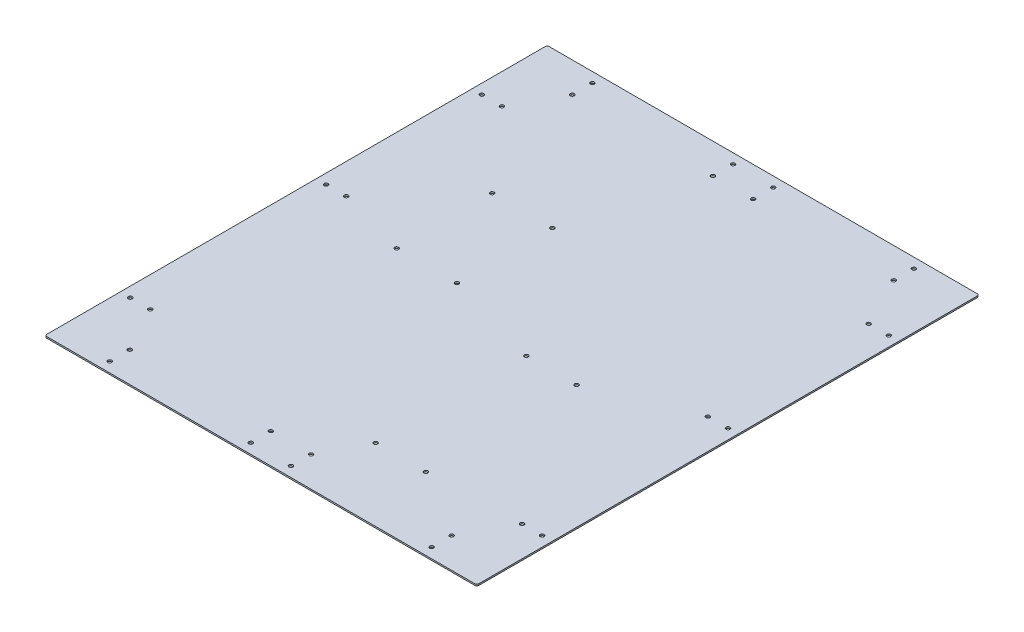
SolidWorks part; units mm, degrees
ref_plane "Front Plane" through (0, 0, 0) normal (0, 0, 1) x (1, 0, 0)
ref_plane "Top Plane" through (0, 0, 0) normal (0, 1, 0) x (1, 0, 0)
ref_plane "Right Plane" through (0, 0, 0) normal (1, 0, 0) x (0, 0, -1)
sketch "Sketch1" plane through (0, 0, 0) normal (0, 1, 0) x (1, 0, 0)
  line L1 (-215, -250) -> (215, -250)
  line L2 (-215, -250) -> (-215, 250)
  line L3 (-215, 250) -> (215, 250)
  line L4 (215, -250) -> (215, 250)
  line L5 (-215, -250) -> (215, 250) construction
  line L6 (-215, 250) -> (215, -250) construction
  point P0 (0, 0)
  dimension "D1" = 430
  dimension "D2" = 500
extrude "Boss-Extrude1" add sketch "Sketch1" along normal blind 1.5
sketch "Sketch6" plane through (0, 1.5, 0) normal (0, 1, 0) x (1, 0, 0)
  circle A0 centre (92.2927, -28) radius 1.95
  circle A1 centre (42.2927, -28) radius 1.95
  circle A2 centre (92.2927, -178) radius 1.95
  circle A3 centre (42.2927, -178) radius 1.95
  dimension "D1" = 50
  dimension "D2" = 150
sketch "Sketch7" plane through (0, 1.5, 0) normal (0, 1, 0) x (1, 0, 0)
  circle A0 centre (-114.98, 95.1924) radius 1.95
  circle A1 centre (-54.98, 95.1924) radius 1.95
  circle A2 centre (-54.98, 0.1924) radius 1.95
  circle A3 centre (-114.98, 0.1924) radius 1.95
  dimension "D1" = 95
  dimension "D2" = 60
sketch "Sketch12" plane through (0, 0, 0) normal (0, -1, 0) x (-1, 0, 0)
  line L0 (215, -250) -> (-215, -250) construction
  line L1 (-215, 250) -> (215, 250) construction
  line L2 (215, 250) -> (215, -250) construction
  line L3 (-215, -250) -> (-215, 250) construction
  circle A0 centre (-185, -175) radius 1.95
  circle A1 centre (-205, 170) radius 1.95
  circle A3 centre (-185, 10) radius 1.95
  circle A4 centre (-205, 10) radius 1.95
  circle A5 centre (-205, -175) radius 1.95
  circle A6 centre (-185, 170) radius 1.95
  circle A7 centre (205, -175) radius 1.95
  circle A8 centre (205, 20) radius 1.95
  circle A9 centre (185, 175) radius 1.95
  circle A10 centre (205, 175) radius 1.95
  circle A11 centre (185, -175) radius 1.95
  circle A12 centre (185, 20) radius 1.95
  circle A13 centre (160.3499, -240) radius 1.95
  circle A14 centre (160.3499, -220) radius 1.95
  circle A15 centre (20, -240) radius 1.95
  circle A16 centre (20, -220) radius 1.95
  circle A17 centre (-20, -220) radius 1.95
  circle A19 centre (-20, -240) radius 1.95
  circle A20 centre (-160, -240) radius 1.95
  circle A21 centre (-160, -220) radius 1.95
  circle A22 centre (160, 220) radius 1.95
  circle A23 centre (160, 240) radius 1.95
  circle A24 centre (20, 220) radius 1.95
  circle A25 centre (20, 240) radius 1.95
  circle A26 centre (-20, 220) radius 1.95
  circle A27 centre (-20, 240) radius 1.95
  circle A28 centre (-160, 220) radius 1.95
  circle A29 centre (-160, 240) radius 1.95
  dimension "D1" = 10
  dimension "D2" = 20
  dimension "D3" = 10
  dimension "D5" = 10
  dimension "D6" = 20
  dimension "D7" = 20
  dimension "D4" = 20
  dimension "D8" = 10
extrude "Cut-Extrude3" cut sketch "Sketch12" against normal blind 50.8
extrude "Cut-Extrude4" cut sketch "Sketch6" against normal blind 50.8
extrude "Cut-Extrude5" cut sketch "Sketch7" against normal blind 50.8
fillet "Fillet1" radius 2 4 edges at (215, 0.75, -250) (215, 0.75, 250) (-215, 0.75, 250) (-215, 0.75, -250)
